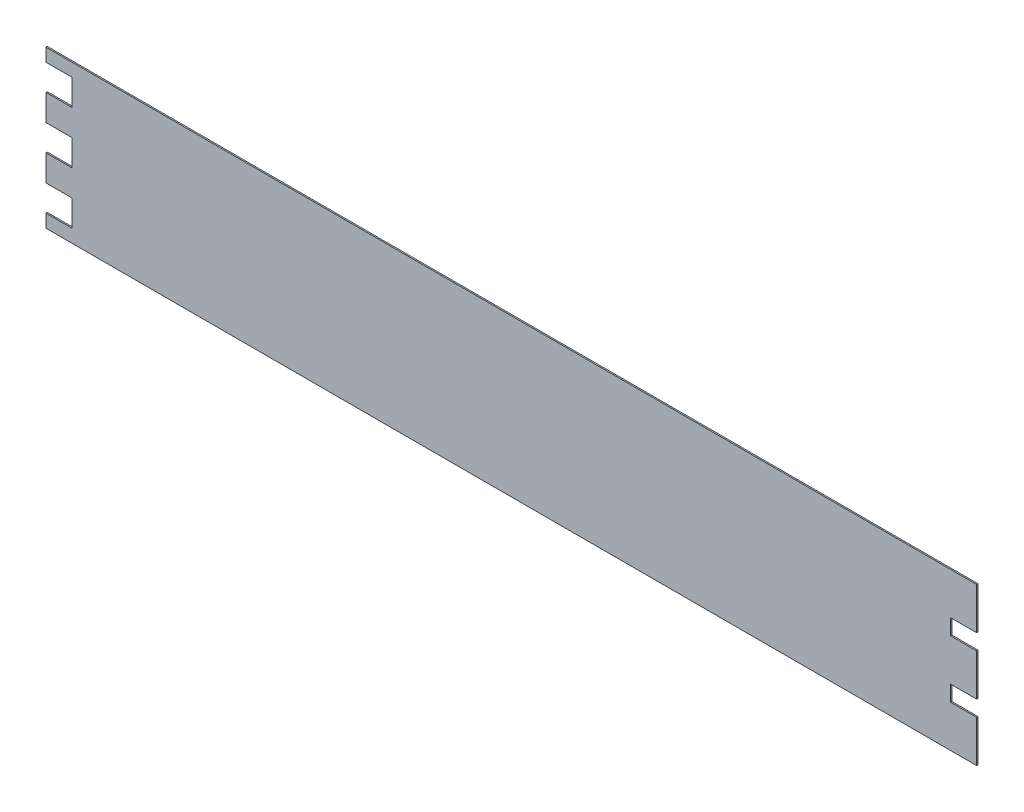
SolidWorks part; units mm, degrees
ref_plane "Front Plane" through (0, 0, 0) normal (0, 0, 1) x (1, 0, 0)
ref_plane "Top Plane" through (0, 0, 0) normal (0, 1, 0) x (1, 0, 0)
ref_plane "Right Plane" through (0, 0, 0) normal (1, 0, 0) x (0, 0, -1)
sketch "Sketch2" plane through (0, 0, 0) normal (0, 0, 1) x (1, 0, 0)
  line L0 (0, 0) -> (5, 0)
  line L1 (5, 0) -> (173, 20)
  line L2 (173, 20) -> (178, 20)
  line L3 (178, 20) -> (178, 50)
  line L4 (178, 50) -> (0, 50)
  line L5 (0, 50) -> (0, 0)
  dimension "D1" = 50
  dimension "D2" = 5
  dimension "D3" = 5
  dimension "D4" = 168
  dimension "D5" = 30
extrude "Boss-Extrude1" add sketch "Sketch2" along normal mid plane 0.25
sketch "Sketch3" plane through (0, 0, 0.125) normal (0, 0, 1) x (1, 0, 0)
  line L1 (0, 47.5) -> (5, 47.5)
  line L2 (0, 47.5) -> (0, 42.5)
  line L3 (0, 42.5) -> (5, 42.5)
  line L4 (5, 47.5) -> (5, 42.5)
  line L5 (178, 50) -> (0, 50) construction
  dimension "D1" = 5
  dimension "D2" = 5
  dimension "D3" = 2.5
extrude "Cut-Extrude1" cut sketch "Sketch3" against normal through all
pattern_linear "LPattern2" count 5 spacing 10 along (0, -1, 0) of "Cut-Extrude1"
sketch "Sketch4" plane through (0, 0, 0.125) normal (0, 0, 1) x (1, 0, 0)
  line L0 (178, 20) -> (178, 50) construction
  line L1 (178, 42) -> (173, 42)
  line L2 (178, 42) -> (178, 39)
  line L3 (178, 39) -> (173, 39)
  line L4 (173, 42) -> (173, 39)
  line L5 (178, 50) -> (0, 50) construction
  dimension "D1" = 5
  dimension "D2" = 3
  dimension "D3" = 8
extrude "Cut-Extrude2" cut sketch "Sketch4" against normal through all
pattern_linear "LPattern3" count 2 spacing 11 along (0, -1, 0) of "Cut-Extrude2"
sketch "Sketch5" plane through (0, 0, 0.125) normal (0, 0, 1) x (1, 0, 0)
  line L1 (178, 20) -> (0, 20)
  line L2 (178, 20) -> (178, 0)
  line L3 (178, 0) -> (0, 0)
  line L4 (0, 20) -> (0, 0)
extrude "Cut-Extrude3" cut sketch "Sketch5" against normal through all
